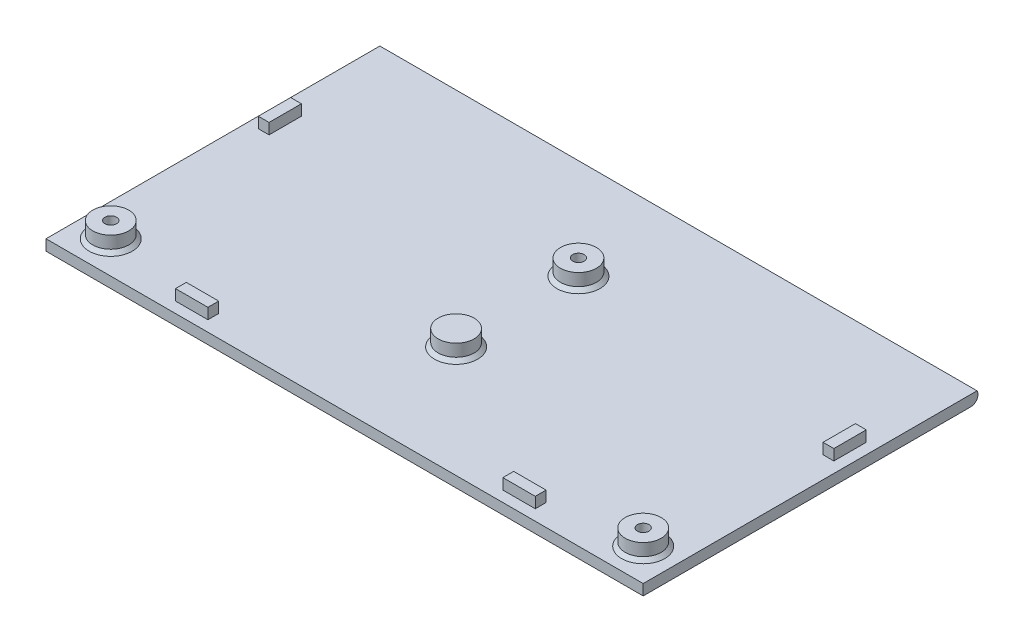
SolidWorks part; units mm, degrees
ref_plane "前视基准面" through (0, 0, 0) normal (0, 0, 1) x (1, 0, 0)
ref_plane "上视基准面" through (0, 0, 0) normal (0, 1, 0) x (1, 0, 0)
ref_plane "右视基准面" through (0, 0, 0) normal (1, 0, 0) x (0, 0, -1)
sketch "草图1" plane through (0, 0, 0) normal (1, 0, 0) x (0, 0, -1)
  line L0 (0, 3) -> (0, 0)
  line L1 (0, 0) -> (95.8, 0)
  line L2 (95.8, 0) -> (92.8, 3)
  line L3 (92.8, 3) -> (0, 3)
  dimension "D1" = 45
  dimension "D2" = 95.8
  dimension "D3" = 3
extrude "凸台-拉伸1" add sketch "草图1" along normal mid plane 166
sketch "草图2" plane through (0, 0, 0) normal (0, 1, 0) x (1, 0, 0)
  line L0 (-74, 0) -> (-74, 9) construction
  line L1 (-74, 9) -> (74, 9) construction
  line L2 (-74, 9) -> (-74, 65) construction
  line L3 (-74, 65) -> (74, 65) construction
  line L4 (74, 9) -> (74, 65) construction
  line L5 (83, 0) -> (-83, 0) construction
  line L6 (-74, 9) -> (-83, 9) construction
  line L7 (-83, 0) -> (-83, 95.8) construction
  line L8 (74, 9) -> (83, 9) construction
  line L9 (83, 0) -> (83, 95.8) construction
  line L10 (0, 65) -> (0, 31) construction
  circle A0 centre (-74, 9) radius 5
  circle A1 centre (74, 9) radius 5
  circle A2 centre (0, 65) radius 5
  circle A3 centre (0, 31) radius 5
  dimension "D3" = 10
  dimension "D1" = 9
  dimension "D2" = 56
  dimension "D4" = 34
extrude "凸台-拉伸2" add sketch "草图2" along normal blind 4.4 from surface starting at face at (0, 3, -46.4)
sketch "草图3" plane through (0, 0, 0) normal (0, 1, 0) x (1, 0, 0)
  circle A0 centre (74, 9) radius 1.6
  circle A1 centre (-74, 9) radius 1.6
  circle A2 centre (0, 65) radius 1.6
  dimension "D1" = 3.2
extrude "切除-拉伸1" cut sketch "草图3" along normal up to next from surface starting at face at (0, 0, -47.9)
chamfer "倒角1" distance 2 angle 45 3 edges at (0, 0, -63.4) (74, 0, -7.4) (-74, 0, -7.4)
sketch "草图4" plane through (0, 0, 0) normal (0, 1, 0) x (1, 0, 0)
  line L0 (80, 3) -> (83, 3) construction
  line L1 (-80, 3) -> (80, 3) construction
  line L2 (-80, 3) -> (-80, 65) construction
  line L3 (-80, 65) -> (80, 65) construction
  line L4 (80, 3) -> (80, 65) construction
  line L5 (83, 92.8) -> (83, 0) construction
  line L6 (80, 3) -> (80, 0) construction
  line L7 (83, 0) -> (-83, 0) construction
  line L8 (-80, 3) -> (-83, 3) construction
  line L9 (-83, 92.8) -> (-83, 0) construction
  line L11 (41, 3) -> (50, 3)
  line L12 (41, 3) -> (41, 6)
  line L13 (41, 6) -> (50, 6)
  line L14 (50, 3) -> (50, 6)
  line L15 (-50, 3) -> (-41, 3)
  line L16 (-50, 3) -> (-50, 6)
  line L17 (-50, 6) -> (-41, 6)
  line L18 (-41, 3) -> (-41, 6)
  line L19 (-80, 65) -> (-77, 65)
  line L20 (-80, 65) -> (-80, 56)
  line L21 (-80, 56) -> (-77, 56)
  line L22 (-77, 65) -> (-77, 56)
  line L23 (80, 65) -> (77, 65)
  line L24 (80, 65) -> (80, 56)
  line L25 (80, 56) -> (77, 56)
  line L26 (77, 65) -> (77, 56)
  point P4 (0, 65)
  dimension "D1" = 3
  dimension "D2" = 30
  dimension "D3" = 30
  dimension "D4" = 3
  dimension "D5" = 9
extrude "凸台-拉伸3" add sketch "草图4" along normal blind 3 from surface starting at face at (0, 3, -36)
chamfer "倒角2" distance 1 angle 45 4 edges at (0, 3, -36) (0, 3, -70) (-74, 3, -14) (74, 3, -14)
fillet "圆角1" radius 2 1 edges at (0, 0, -95.8)
